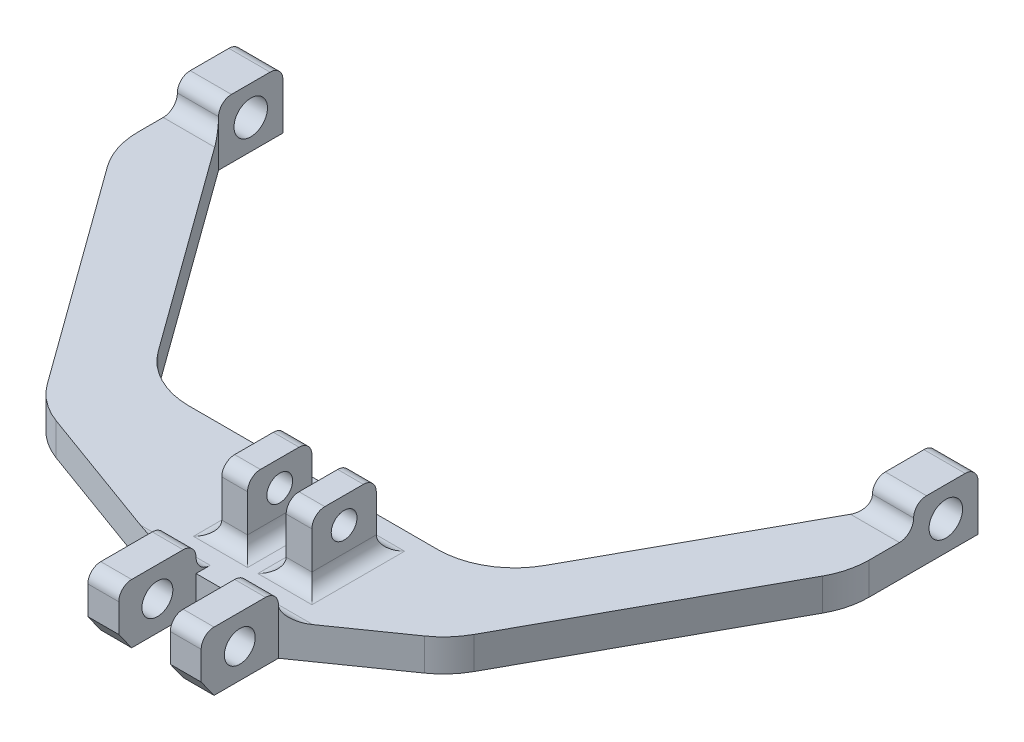
SolidWorks part; units mm, degrees
material "AISI 4130 Steel, annealed at 865C"
ref_plane "Front Plane" through (0, 0, 0) normal (0, 0, 1) x (1, 0, 0)
ref_plane "Top Plane" through (0, 0, 0) normal (0, 1, 0) x (1, 0, 0)
ref_plane "Right Plane" through (0, 0, 0) normal (1, 0, 0) x (0, 0, -1)
sketch "Sketch2" plane through (0, 0, 0) normal (0, 1, 0) x (1, 0, 0)
  line L1 (72.5775, -150.1384) -> (147.7529, -177.5)
  line L2 (147.7529, -177.5) -> (147.7529, -207.5)
  line L3 (147.7529, -207.5) -> (159.7529, -207.5)
  line L4 (159.7529, -207.5) -> (159.7529, -177.5)
  line L5 (159.7529, -177.5) -> (169.7529, -177.5)
  line L6 (169.7529, -177.5) -> (179.7529, -177.5)
  line L9 (179.7529, -177.5) -> (179.7529, -207.5)
  line L10 (179.7529, -207.5) -> (191.7529, -207.5)
  line L11 (191.7529, -207.5) -> (191.7529, -177.5)
  line L12 (191.7529, -177.5) -> (230.8293, -150.1384)
  line L14 (86.6653, -122.5) -> (216.2808, -122.5)
  line L18 (0, -50) -> (72.5775, -150.1384)
  line L20 (16, -25) -> (86.6653, -122.5)
  line L23 (269.9194, -25) -> (216.2808, -122.5)
  line L24 (285.9194, -50) -> (230.8293, -150.1384)
  line L28 (285.9194, 0) -> (285.9194, -50)
  line L34 (0, 0) -> (16, 0)
  line L35 (16, 0) -> (16, -25)
  line L36 (269.9194, -25) -> (269.9194, 0)
  line L37 (269.9194, 0) -> (285.9194, 0)
  line L39 (0, 0) -> (0, -50)
  point P0 (8, 0)
  point P2 (169.7529, -192.5)
  point P3 (8, -12.5)
  point P9 (277.9194, -12.5)
  point P16 (159.7529, -192.5)
  point P29 (277.9194, 0)
  point P30 (16, -12.5)
  dimension "D3" = 30
  dimension "D4" = 12
  dimension "D9" = 10
  dimension "D6" = 145
  dimension "D5" = 80
  dimension "D8" = 160
  dimension "D18" = 25
  dimension "D7" = 25
  dimension "D13" = 16
  dimension "D2" = 55
  dimension "D12" = 180
  dimension "D10" = 242
  dimension "D11" = 210
extrude "Boss-Extrude1" add sketch "Sketch2" along normal blind 12.5
sketch "Sketch5" plane through (0, 12.5, 0) normal (0, 1, 0) x (1, 0, 0)
  line L0 (159.7529, -207.5) -> (159.7529, -177.5) construction
  line L1 (152.2529, -135) -> (162.2529, -135)
  line L2 (152.2529, -135) -> (152.2529, -160)
  line L3 (152.2529, -160) -> (162.2529, -160)
  line L4 (162.2529, -135) -> (162.2529, -160)
  line L5 (177.2529, -135) -> (187.2529, -135)
  line L6 (177.2529, -135) -> (177.2529, -160)
  line L7 (177.2529, -160) -> (187.2529, -160)
  line L8 (187.2529, -135) -> (187.2529, -160)
  line L9 (162.2529, -147.5) -> (177.2529, -147.5) construction
  line L10 (159.7529, -192.5) -> (179.7529, -192.5) construction
  line L11 (179.7529, -177.5) -> (179.7529, -207.5) construction
  point P10 (159.7529, -192.5)
  point P11 (162.2529, -147.5)
  point P18 (169.7529, -192.5)
  point P19 (169.7529, -147.5)
  dimension "D1" = 45
  dimension "D2" = 10
  dimension "D3" = 25
  dimension "D4" = 15
extrude "Boss-Extrude2" add sketch "Sketch5" along normal blind 25
sketch "Sketch7" plane through (0, 12.5, 0) normal (0, 1, 0) x (1, 0, 0)
  line L1 (147.7529, -207.5) -> (159.7529, -207.5)
  line L2 (147.7529, -207.5) -> (147.7529, -177.5)
  line L3 (147.7529, -177.5) -> (159.7529, -177.5)
  line L4 (159.7529, -207.5) -> (159.7529, -177.5)
  line L5 (179.7529, -207.5) -> (191.7529, -207.5)
  line L6 (179.7529, -207.5) -> (179.7529, -177.5)
  line L7 (179.7529, -177.5) -> (191.7529, -177.5)
  line L8 (191.7529, -207.5) -> (191.7529, -177.5)
extrude "Boss-Extrude4" add sketch "Sketch7" along normal blind 10.5
sketch "Sketch8" plane through (147.7529, 0, 0) normal (-1, 0, 0) x (0, 0, 1)
  line L0 (177.5, 23) -> (207.5, 23) construction
  line L1 (207.5, 23) -> (207.5, 0) construction
  circle A0 centre (192.5, 11.5) radius 6
  point P4 (192.5, 23)
  point P7 (207.5, 11.5)
  dimension "D1" = 12
extrude "Cut-Extrude1" cut sketch "Sketch8" against normal through all
sketch "Sketch11" plane through (0, 12.5, 0) normal (0, 1, 0) x (1, 0, 0)
  line L0 (285.9194, -50) -> (285.9194, 0) construction
  line L1 (0, 0) -> (16, 0)
  line L2 (0, 0) -> (0, -25)
  line L3 (0, -25) -> (16, -25)
  line L4 (16, 0) -> (16, -25)
  line L5 (269.9194, 0) -> (285.9194, 0)
  line L6 (269.9194, 0) -> (269.9194, -25)
  line L7 (269.9194, -25) -> (285.9194, -25)
  line L8 (285.9194, 0) -> (285.9194, -25)
extrude "Boss-Extrude6" add sketch "Sketch11" along normal blind 10.5
sketch "Sketch12" plane through (0, 0, 0) normal (-1, 0, 0) x (0, 0, 1)
  line L0 (0, 23) -> (25, 23) construction
  line L1 (0, 0) -> (50, 0) construction
  circle A0 centre (12.5, 11.5) radius 6.5
  point P5 (12.5, 23)
  dimension "D1" = 13
  dimension "D2" = 11.5
extrude "Cut-Extrude3" cut sketch "Sketch12" against normal through all
sketch "Sketch13" plane through (152.2529, 0, 0) normal (-1, 0, 0) x (0, 0, 1)
  line L0 (50, 12.5) -> (150.1384, 12.5) construction
  line L1 (135, 37.5) -> (160, 37.5) construction
  circle A0 centre (147.5, 27.5) radius 5
  point P7 (147.5, 37.5)
  dimension "D1" = 10
  dimension "D2" = 15
extrude "Cut-Extrude4" cut sketch "Sketch13" against normal through all
fillet "Fillet2" radius 30 6 edges at (285.9194, 6.25, 50) (230.8293, 6.25, 150.1384) (216.2808, 6.25, 122.5) (86.6653, 6.25, 122.5) (72.5775, 6.25, 150.1384) (0, 6.25, 50)
fillet "Fillet3" radius 5 12 edges at (185.7529, 23, 207.5) (153.7529, 23, 207.5) (185.7529, 23, 177.5) (153.7529, 23, 177.5) (157.2529, 37.5, 135) (157.2529, 37.5, 160) (182.2529, 37.5, 135) (182.2529, 37.5, 160) (277.9194, 23, 0) (277.9194, 23, 25) (8, 23, 0) (8, 23, 25)
fillet "Fillet4" radius 5.5 12 edges at (153.7529, 12.5, 177.5) (185.7529, 12.5, 177.5) (182.2529, 12.5, 135) (157.2529, 12.5, 135) (182.2529, 12.5, 160) (157.2529, 12.5, 160) (8, 12.5, 25) (277.9194, 12.5, 25) (152.2529, 12.5, 147.5) (187.2529, 12.5, 147.5) (177.2529, 12.5, 147.5) (162.2529, 12.5, 147.5)
chamfer "Chamfer1" distance 5 distance2 7 2 edges at (185.7529, 0, 207.5) (153.7529, 0, 207.5) first distance on face at (153.8575, 0, 109.6991)
equation "\"LCA Rear\"= 210"
equation "\"UCA Front\"= 242"
equation "\"UCA out\"= 180"
equation "\"D12@Sketch2\"=\"UCA out\""
equation "\"D10@Sketch2\"=\"UCA Front\""
equation "\"D11@Sketch2\"=\"LCA Rear\""
